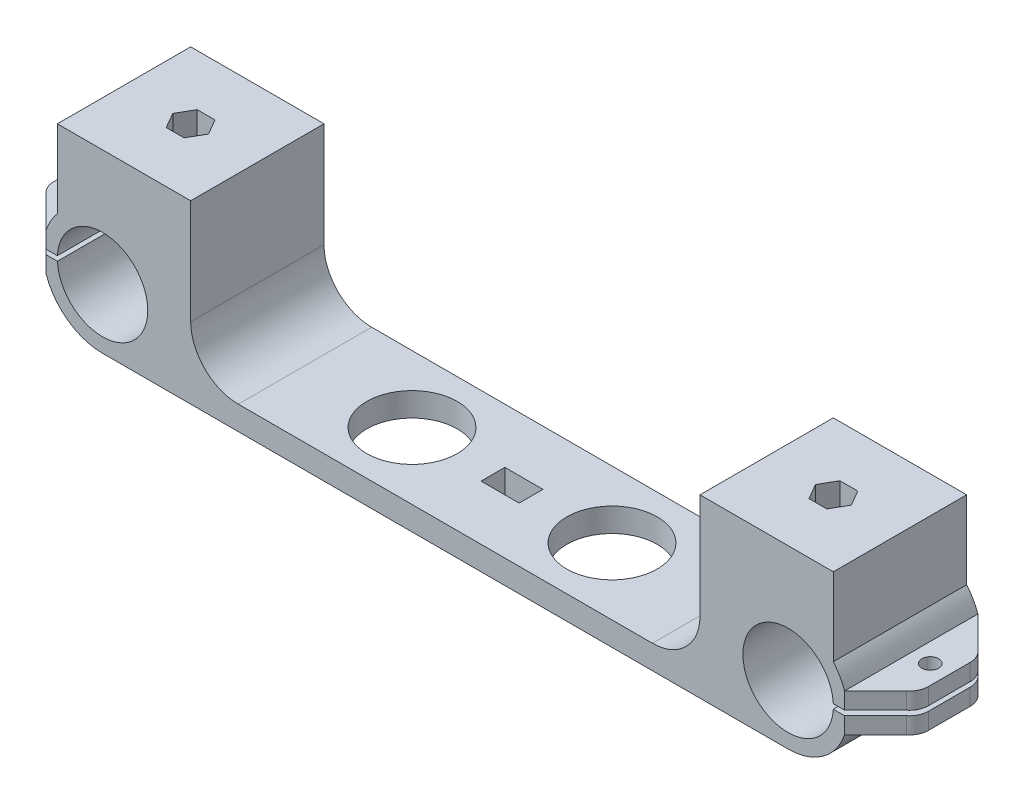
SolidWorks part; units mm, degrees
ref_plane "Front Plane" through (0, 0, 0) normal (0, 0, 1) x (1, 0, 0)
ref_plane "Top Plane" through (0, 0, 0) normal (0, 1, 0) x (1, 0, 0)
ref_plane "Right Plane" through (0, 0, 0) normal (1, 0, 0) x (0, 0, -1)
sketch "Sketch7" plane through (0, 0, 0) normal (0, 0, 1) x (1, 0, 0)
  line L0 (-29.0094, -4.6853) -> (114.9906, -4.6853)
  line L1 (-10.4962, 0.3147) -> (96.4774, 0.3147)
  line L2 (126.8333, 3.8147) -> (134.8333, 3.8147)
  line L3 (134.8333, 3.8147) -> (134.8333, 7.3147)
  line L4 (134.8333, 7.3147) -> (127.4806, 7.3147)
  line L5 (127.4806, 8.3147) -> (134.8333, 8.3147)
  line L6 (134.8333, 8.3147) -> (134.8333, 11.8147)
  line L7 (134.8333, 11.8147) -> (126.8333, 11.8147)
  line L8 (127.4806, 7.3147) -> (124.4774, 7.3147)
  line L9 (127.4806, 8.3147) -> (124.4774, 8.3147)
  line L10 (42.9906, -4.6853) -> (42.9906, 54.826) construction
  line L11 (-41.4994, 8.3147) -> (-38.4962, 8.3147)
  line L12 (-41.4994, 7.3147) -> (-38.4962, 7.3147)
  line L13 (-40.8521, 3.8147) -> (-48.8521, 3.8147)
  line L14 (-48.8521, 7.3147) -> (-41.4994, 7.3147)
  line L15 (-48.8521, 3.8147) -> (-48.8521, 7.3147)
  line L16 (-48.8521, 8.3147) -> (-48.8521, 11.8147)
  line L17 (-41.4994, 8.3147) -> (-48.8521, 8.3147)
  line L18 (-48.8521, 11.8147) -> (-40.8521, 11.8147)
  line L19 (-38.4962, 15.9541) -> (-38.4962, 32.3147)
  line L20 (-38.4962, 32.3147) -> (-10.4962, 32.3147)
  line L21 (-10.4962, 32.3147) -> (-10.4962, 0.3147)
  line L22 (96.4774, 32.3147) -> (96.4774, 0.3147)
  line L23 (124.4774, 15.9541) -> (124.4774, 32.3147)
  line L24 (124.4774, 32.3147) -> (96.4774, 32.3147)
  arc A0 (124.4774, 8.3147) -> (124.4774, 7.3147) centre (114.9906, 7.8147) ccw
  arc A1 (-38.4962, 7.3147) -> (-38.4962, 8.3147) centre (-29.0094, 7.8147) ccw
  arc A2 (114.9906, -4.6853) -> (126.8333, 3.8147) centre (114.9906, 7.8147) ccw
  arc A3 (-38.4962, 15.9541) -> (-40.8521, 11.8147) centre (-29.0094, 7.8147) ccw
  arc A4 (-40.8521, 3.8147) -> (-29.0094, -4.6853) centre (-29.0094, 7.8147) ccw
  arc A6 (126.8333, 11.8147) -> (124.4774, 15.9541) centre (114.9906, 7.8147) ccw
  dimension "D2" = 19
  dimension "D3" = 25
  dimension "D11" = 28
  dimension "D1" = 144
  dimension "D4" = 5
  dimension "D5" = 3.5
  dimension "D6" = 3.5
  dimension "D7" = 1
  dimension "D8" = 0.5
  dimension "D9" = 8
  dimension "D10" = 8
  dimension "D12" = 32
extrude "Boss-Extrude3" add sketch "Sketch7" along normal blind 28
fillet "Fillet1" radius 10 2 edges at (96.4774, 0.3147, 14) (-10.4962, 0.3147, 14)
sketch "Sketch8" plane through (0, 0.3147, 0) normal (0, 1, 0) x (1, 0, 0)
  line L0 (42.9906, 0) -> (42.9906, -28) construction
  line L1 (86.4774, 0) -> (-0.4962, 0) construction
  line L2 (86.4774, -28) -> (-0.4962, -28) construction
  line L3 (86.4774, -14) -> (-0.4962, -14) construction
  line L4 (38.9906, -11.5) -> (46.9906, -11.5)
  line L5 (38.9906, -11.5) -> (38.9906, -16.5)
  line L6 (38.9906, -16.5) -> (46.9906, -16.5)
  line L7 (46.9906, -11.5) -> (46.9906, -16.5)
  line L8 (86.4774, -28) -> (86.4774, 0) construction
  line L9 (-0.4962, 0) -> (-0.4962, -28) construction
  circle A0 centre (63.9906, -14) radius 9.5
  circle A1 centre (21.9906, -14) radius 9.5
  dimension "D5" = 19
  dimension "D7" = 21
  dimension "D1" = 5
  dimension "D2" = 8
  dimension "D3" = 4
  dimension "D4" = 2.5
  dimension "D6" = 21
extrude "Cut-Extrude4" cut sketch "Sketch8" against normal up to surface (5 mm away) up to face at (42.9906, -4.6853, 14)
sketch "Sketch9" plane through (0, 11.8147, 0) normal (0, 1, 0) x (1, 0, 0)
  line L0 (130.8333, 0) -> (130.8333, -28) construction
  line L1 (134.8333, 0) -> (126.8333, 0) construction
  line L2 (134.8333, -28) -> (126.8333, -28) construction
  line L3 (-44.8521, 0) -> (-44.8521, -28) construction
  line L4 (-40.8521, 0) -> (-48.8521, 0) construction
  line L5 (-40.8521, -28) -> (-48.8521, -28) construction
  circle A0 centre (130.8333, -14) radius 1.75
  circle A3 centre (-44.8521, -14) radius 1.75
  dimension "D1" = 3.5
extrude "Cut-Extrude5" cut sketch "Sketch9" against normal blind 20
sketch "Sketch10" plane through (0, 32.3147, 0) normal (0, 1, 0) x (1, 0, 0)
  line L0 (124.4774, -14) -> (-38.4962, -14) construction
  line L1 (124.4774, -28) -> (124.4774, 0) construction
  line L2 (-38.4962, -28) -> (-38.4962, 0) construction
  line L3 (110.4906, 0) -> (110.4906, -28) construction
  line L4 (124.4774, 0) -> (96.4774, 0) construction
  line L5 (124.4774, -28) -> (96.4774, -28) construction
  line L6 (-24.5094, 0) -> (-24.5094, -28) construction
  line L7 (-10.4962, 0) -> (-38.4962, 0) construction
  line L8 (-10.4962, -28) -> (-38.4962, -28) construction
  line L9 (86.4774, 0) -> (-0.4962, 0) construction
  circle A0 centre (110.4906, -14) radius 1.75
  circle A1 centre (-24.5094, -14) radius 1.75
  point P30 (42.9906, 0)
  dimension "D1" = 3.5
  dimension "D2" = 135
  dimension "D3" = 67.5
extrude "Cut-Extrude6" cut sketch "Sketch10" against normal blind 10
sketch "Sketch12" plane through (0, 11.8147, 0) normal (0, 1, 0) x (1, 0, 0)
  line L0 (130.8333, -21.5) -> (126.8333, -21.5)
  line L1 (126.8333, -28) -> (126.8333, 0) construction
  line L2 (126.8333, -21.5) -> (126.8333, -28)
  line L3 (126.8333, -28) -> (134.8333, -28)
  line L4 (134.8333, -28) -> (134.8333, -21.5)
  line L5 (134.8333, -28) -> (134.8333, 0) construction
  line L6 (134.8333, -21.5) -> (130.8333, -21.5)
  line L7 (130.8333, -6.5) -> (126.8333, -6.5)
  line L8 (126.8333, -6.5) -> (126.8333, 0)
  line L9 (126.8333, 0) -> (134.8333, 0)
  line L10 (134.8333, 0) -> (134.8333, -6.5)
  line L11 (134.8333, -6.5) -> (130.8333, -6.5)
  line L12 (-44.8521, -6.5) -> (-40.8521, -6.5)
  line L13 (-40.8521, -28) -> (-40.8521, 0) construction
  line L14 (-40.8521, -6.5) -> (-40.8521, 0)
  line L15 (-40.8521, 0) -> (-48.8521, 0)
  line L16 (-48.8521, 0) -> (-48.8521, -6.5)
  line L17 (-48.8521, -28) -> (-48.8521, 0) construction
  line L18 (-48.8521, -6.5) -> (-44.8521, -6.5)
  line L19 (-44.8521, -21.5) -> (-48.8521, -21.5)
  line L20 (-48.8521, -21.5) -> (-48.8521, -28)
  line L21 (-48.8521, -28) -> (-40.8521, -28)
  line L22 (-40.8521, -28) -> (-40.8521, -21.5)
  line L23 (-40.8521, -21.5) -> (-44.8521, -21.5)
  circle A0 centre (130.8333, -14) radius 7.5 construction
  circle A1 centre (-44.8521, -14) radius 7.5 construction
  dimension "D1" = 15
extrude "Cut-Extrude8" cut sketch "Sketch12" against normal blind 10
chamfer "Chamfer1" distance 6.5 angle 45 8 edges at (126.8333, 10.0647, 6.5) (126.8333, 5.5647, 6.5) (126.8333, 5.5647, 21.5) (126.8333, 10.0647, 21.5) (-40.8521, 5.5647, 21.5) (-40.8521, 5.5647, 6.5) (-40.8521, 10.0647, 6.5) (-40.8521, 10.0647, 21.5)
fillet "Fillet3" radius 4 8 edges at (134.8333, 10.0647, 21.5) (134.8333, 5.5647, 21.5) (134.8333, 5.5647, 6.5) (134.8333, 10.0647, 6.5) (-48.8521, 5.5647, 6.5) (-48.8521, 5.5647, 21.5) (-48.8521, 10.0647, 21.5) (-48.8521, 10.0647, 6.5)
sketch "Sketch13" plane through (0, 32.3147, 0) normal (0, 1, 0) x (1, 0, 0)
  line L0 (124.4774, -28) -> (96.4774, -28) construction
  line L1 (108.6142, -17.25) -> (112.367, -17.25)
  line L2 (112.367, -17.25) -> (114.2434, -14)
  line L3 (114.2434, -14) -> (112.367, -10.75)
  line L4 (112.367, -10.75) -> (108.6142, -10.75)
  line L5 (108.6142, -10.75) -> (106.7378, -14)
  line L6 (106.7378, -14) -> (108.6142, -17.25)
  line L7 (-20.7566, -14) -> (-22.633, -10.75)
  line L8 (-22.633, -10.75) -> (-26.3858, -10.75)
  line L9 (-26.3858, -10.75) -> (-28.2622, -14)
  line L10 (-28.2622, -14) -> (-26.3858, -17.25)
  line L11 (-26.3858, -17.25) -> (-22.633, -17.25)
  line L12 (-22.633, -17.25) -> (-20.7566, -14)
  circle A0 centre (110.4906, -14) radius 3.25 construction
  circle A1 centre (-24.5094, -14) radius 3.25 construction
  dimension "D1" = 6.5
extrude "Cut-Extrude9" cut sketch "Sketch13" against normal blind 5
sketch "Sketch14" [suppressed] plane through (0, 0, 28) normal (0, 0, 1) x (1, 0, 0)
  line L1 (-82.4893, 23.5071) -> (44.7899, 150.7863)
  line L2 (-82.4893, 23.5071) -> (44.7899, -103.7721)
  line L3 (44.7899, -103.7721) -> (172.0692, 23.5071)
  line L4 (44.7899, 150.7863) -> (172.0692, 23.5071)
  line L6 (124.4774, 32.3147) -> (96.4774, 32.3147) construction
  dimension "D1" = 180
  dimension "D2" = 180
  dimension "D3" = 45
sketch "Sketch11" plane through (0, 0, 28) normal (0, 0, 1) x (1, 0, 0)
  line L1 (-81.97, 61.9449) -> (93.8843, 61.9449)
  line L2 (-81.97, 61.9449) -> (-81.97, -12.8023)
  line L3 (-81.97, -12.8023) -> (93.8843, -12.8023)
  line L4 (93.8843, 61.9449) -> (93.8843, -12.8023)
extrude "Cut-Extrude7" [suppressed] cut sketch "Sketch11" against normal blind 56
